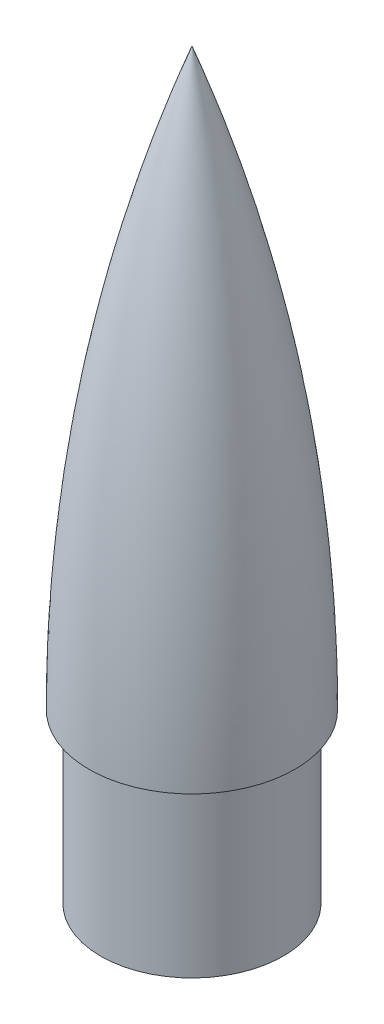
SolidWorks part; units mm, degrees
other "NoseCone"
ref_plane "Front Plane" through (0, 0, 0) normal (0, 0, 1) x (1, 0, 0)
ref_plane "Top Plane" through (0, 0, 0) normal (0, 1, 0) x (1, 0, 0)
ref_plane "Right Plane" through (0, 0, 0) normal (1, 0, 0) x (0, 0, -1)
sketch "Sketch1" plane through (0, 0, 0) normal (0, 0, 1) x (1, 0, 0)
  line L0 (0, -0.9433) -> (0, 351.1087) construction
  line L1 (-38.1, 0) -> (-34.1, 0)
  line L2 (-38.1, 0) -> (-38.1, 70)
  line L3 (-38.1, 70) -> (-43, 70)
  line L4 (-43, 4.6087) -> (-43, 50004.6087) construction
  line L5 (0, 298.2233) -> (0, 310)
  line L6 (-34.1, 0) -> (-34.1, 151.922)
  arc A0 (-43, 70) -> (0, 310) centre (648.2674, 70) cw
  arc A1 (-34.1, 151.922) -> (0, 298.2233) centre (648.2674, 70) cw
  dimension "D6" = 4
  dimension "D1" = 4
  dimension "D2" = 38.1
  dimension "D3" = 70
  dimension "D4" = 43
  dimension "D5" = 240
revolve "Cone" add sketch "Sketch1" angle 360 about L0
sketch "Sketch4" plane through (0, 0, 0) normal (0, -1, 0) x (1, 0, 0)
  line L0 (0, 0) -> (0, -50000) construction
  line L1 (15, 15.1) -> (-15, 15.1)
  line L2 (-15, 15.1) -> (-15, 30.6237)
  line L3 (15, 15.1) -> (15, 30.6237)
  line L4 (7.1801, 15.1) -> (-49992.8199, 15.1) construction
  circle A0 centre (0, 0) radius 34.1 construction
  arc A1 (-15, 30.6237) -> (15, 30.6237) centre (0, 0) ccw
  point P3 (0, 34.1)
  point P7 (0, 15.1)
  dimension "D2" = 19
extrude "Boss-Extrude2" add sketch "Sketch4" against normal blind 70 separate body contours A1 L3 L1 L2
fillet "Fillet1" radius 1 2 edges at (-15, 35, 15.1) (15, 35, 15.1)
shell "Shell1" thickness 2 removed face at (0, 0, 9.7516) removed face at (0, 70, 9.7516)
ref_plane "Plane2" through (-14, 70, 13.1) normal (0, -1, 0) x (-1, 0, 0)
sketch "Sketch5" plane through (0, 70, 0) normal (0, 1, 0) x (1, 0, 0)
  line L0 (-29.3053, -13.1) -> (29.3053, -13.1)
  line L2 (-29.3053, -13.1) -> (-31.4965, -11.1)
  line L3 (-31.4965, -11.1) -> (31.2452, -11.1)
  line L4 (31.2452, -11.1) -> (29.3053, -13.1)
  arc A0 (17, -27.2288) -> (-17, -27.2288) centre (0, 0) ccw construction
  dimension "D1" = 2
extrude "Boss-Extrude6" add sketch "Sketch5" against normal blind 69
